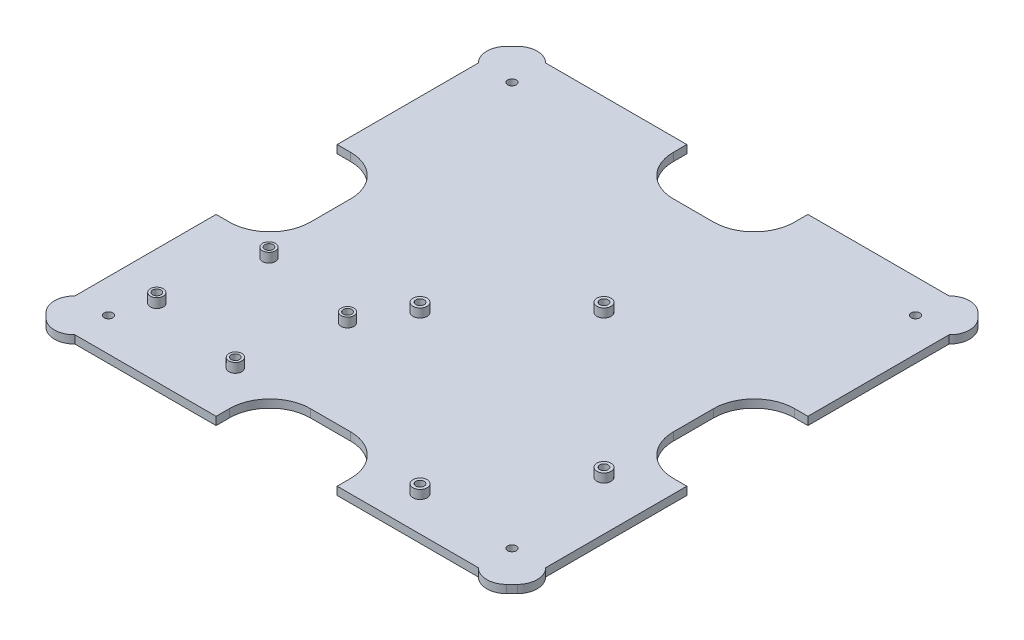
SolidWorks part; units mm, degrees
ref_plane "Front Plane" through (0, 0, 0) normal (0, 0, 1) x (1, 0, 0)
ref_plane "Top Plane" through (0, 0, 0) normal (0, 1, 0) x (1, 0, 0)
ref_plane "Right Plane" through (0, 0, 0) normal (1, 0, 0) x (0, 0, -1)
sketch "Sketch1" plane through (0, 0, 0) normal (0, 1, 0) x (1, 0, 0)
  line L0 (132.5, 75) -> (87.5, 75)
  line L5 (-75, 132.5) -> (75, 132.5)
  line L6 (-75, 132.5) -> (-75, 87.5)
  line L7 (-75, 87.5) -> (75, 87.5)
  line L8 (75, 132.5) -> (75, 87.5)
  line L9 (132.5, 75) -> (132.5, -75)
  line L10 (132.5, -75) -> (87.5, -75)
  line L11 (87.5, 75) -> (87.5, -75)
  line L12 (75, -132.5) -> (75, -87.5)
  line L13 (75, -132.5) -> (-75, -132.5)
  line L14 (-75, -132.5) -> (-75, -87.5)
  line L15 (75, -87.5) -> (-75, -87.5)
  line L16 (-132.5, -75) -> (-87.5, -75)
  line L17 (-132.5, -75) -> (-132.5, 75)
  line L18 (-132.5, 75) -> (-87.5, 75)
  line L19 (-87.5, -75) -> (-87.5, 75)
  line L20 (0, 122.5) -> (0, 87.5) construction
  line L21 (0, 132.5) -> (0, 122.5) construction
  circle A0 centre (0, 0) radius 122.5
  point P7 (0, 87.5)
  point P23 (0, 0)
  dimension "D1" = 245
  dimension "D4" = 35
  dimension "D2" = 150
  dimension "D5" = 10
  dimension "D3" = 4
extrude "shell-boss" add sketch "Sketch1" along normal blind 3 contours L12 A0 L10 L11 L0 L8 L7 L6 L18 L19 L16 L14 L15 region at (0, 0, 0)
fillet "shell-filet" radius 7.5 8 edges at (-96.8569, 1.5, 75) (-96.8569, 1.5, -75) (-75, 1.5, -96.8569) (75, 1.5, -96.8569) (96.8569, 1.5, -75) (96.8569, 1.5, 75) (75, 1.5, 96.8569) (-75, 1.5, 96.8569)
sketch "Sketch5" plane through (0, 3, 0) normal (0, 1, 0) x (1, 0, 0)
  line L2 (-87.5, 0) -> (87.5, 0) construction
  line L3 (-87.5, -75) -> (-87.5, 75) construction
  line L4 (87.5, 75) -> (87.5, -75) construction
  circle A0 centre (75, -75) radius 1.6
  circle A2 centre (-75, -75) radius 1.6
  arc A3 (85.6059, -87.6235) -> (87.6235, -85.6059) centre (0, 0) ccw construction
  circle A9 centre (75, 75) radius 1.6
  circle A10 centre (-75, 75) radius 1.6
  dimension "D1" = 150
  dimension "D2" = 3.2
  dimension "D4" = 106.066
  dimension "D3" = 150
extrude "shell-pillar-hole" cut sketch "Sketch5" against normal through all both and the other way through all
sketch "Sketch16" plane through (0, 3, 0) normal (0, 1, 0) x (1, 0, 0)
  line L0 (16.1138, 18.065) -> (-18.065, -16.1138) construction
  line L1 (16.1138, 18.065) -> (69.241, -35.0622) construction
  line L2 (69.241, -35.0622) -> (40.3605, -74.5394) construction
  line L3 (40.3605, -74.5394) -> (-18.065, -16.1138) construction
  line L4 (54.8008, -54.8008) -> (86.6206, -86.6206) construction
  line L5 (0, 0) -> (-86.6206, 86.6206) construction
  circle A4 centre (16.1138, 18.065) radius 2.625
  circle A5 centre (-18.065, -16.1138) radius 2.625
  circle A6 centre (69.241, -35.0622) radius 2.625
  circle A7 centre (40.3605, -74.5394) radius 2.625
  arc A8 (-85.6059, 87.6235) -> (-87.6235, 85.6059) centre (0, 0) ccw construction
  arc A9 (85.6059, -87.6235) -> (87.6235, -85.6059) centre (0, 0) ccw construction
  point P13 (-0.9756, 0.9756)
  dimension "D4" = 75.1332
  dimension "D2" = 48.3362
  dimension "D1" = 5.25
  dimension "D3" = 82.6262
  dimension "D5" = 45
extrude "arduino-mount-boss" add sketch "Sketch16" along normal blind 3.25
sketch "Sketch20" plane through (0, 3, 0) normal (0, 1, 0) x (1, 0, 0)
  line L0 (-37.2464, 19.4268) -> (-58.5183, -101.2121) construction
  line L1 (-63.6554, -26.6879) -> (-28.2023, -32.9392) construction
  line L2 (-28.2023, -32.9392) -> (-34.4536, -68.3923) construction
  line L3 (-34.4536, -68.3923) -> (-69.9067, -62.1409) construction
  line L4 (-69.9067, -62.1409) -> (-63.6554, -26.6879) construction
  line L9 (-52.1802, -65.2666) -> (-72.2702, -61.7242) construction
  line L11 (-52.1802, -65.2666) -> (-32.0901, -68.809) construction
  line L21 (-63.6554, -26.6879) -> (-63.2386, -24.3243) construction
  line L23 (-28.2023, -32.9392) -> (-27.7855, -30.5757) construction
  circle A16 centre (-63.6554, -26.6879) radius 2.4
  circle A17 centre (-28.2023, -32.9392) radius 2.4
  circle A18 centre (-34.4536, -68.3923) radius 2.4
  circle A19 centre (-69.9067, -62.1409) radius 2.4
  point P2 (-45.9288, -29.8135)
  dimension "D1" = 50
  dimension "D3" = 4.8
  dimension "D2" = 36
sketch "Sketch22" plane through (0, 6.25, 0) normal (0, 1, 0) x (1, 0, 0)
  circle A0 centre (16.1138, 18.065) radius 1.55
  circle A1 centre (-18.065, -16.1138) radius 1.55
  circle A2 centre (69.241, -35.0622) radius 1.55
  circle A3 centre (40.3605, -74.5394) radius 1.55
  dimension "D1" = 3.1
extrude "arduino-cut" cut sketch "Sketch22" against normal up to surface (6.25 mm away) up to face at (-75, 0, 76.6)
extrude "Boss-Extrude9" add sketch "Sketch20" along normal blind 3.5
sketch "Sketch37" plane through (0, 6.5, 0) normal (0, 1, 0) x (1, 0, 0)
  circle A0 centre (-63.6554, -26.6879) radius 1.55
  circle A1 centre (-28.2023, -32.9392) radius 1.55
  circle A2 centre (-69.9067, -62.1409) radius 1.55
  circle A3 centre (-34.4536, -68.3923) radius 1.55
  dimension "D1" = 3.1
extrude "Cut-Extrude4" cut sketch "Sketch37" against normal up to surface (6.5 mm away) up to face at (16.1138, 0, -16.515)
sketch "Sketch38" plane through (0, 0, 0) normal (0, -1, 0) x (1, 0, 0)
  line L0 (75, 87.5) -> (-75, 87.5) construction
  line L1 (22.5, 87.5) -> (-22.5, 87.5)
  line L2 (22.5, 87.5) -> (22.5, 67.5)
  line L3 (22.5, 67.5) -> (-22.5, 67.5)
  line L4 (-22.5, 87.5) -> (-22.5, 67.5)
  line L5 (87.5, -22.5) -> (67.5, -22.5)
  line L6 (87.5, -22.5) -> (87.5, 22.5)
  line L7 (87.5, 22.5) -> (67.5, 22.5)
  line L8 (67.5, -22.5) -> (67.5, 22.5)
  line L9 (-22.5, -87.5) -> (-22.5, -67.5)
  line L10 (-22.5, -87.5) -> (22.5, -87.5)
  line L11 (22.5, -87.5) -> (22.5, -67.5)
  line L12 (-22.5, -67.5) -> (22.5, -67.5)
  line L13 (-87.5, 22.5) -> (-67.5, 22.5)
  line L14 (-87.5, 22.5) -> (-87.5, -22.5)
  line L15 (-87.5, -22.5) -> (-67.5, -22.5)
  line L16 (-67.5, 22.5) -> (-67.5, -22.5)
  point P6 (0, 87.5)
  point P7 (0, 87.5)
  point P23 (0, 0)
  dimension "D1" = 45
  dimension "D2" = 20
  dimension "D3" = 4
extrude "Cut-Extrude5" cut sketch "Sketch38" against normal through all both and the other way through all
fillet "Fillet1" radius 15 8 edges at (-67.5, 1.5, -22.5) (-67.5, 1.5, 22.5) (22.5, 1.5, -67.5) (-22.5, 1.5, -67.5) (67.5, 1.5, -22.5) (67.5, 1.5, 22.5) (22.5, 1.5, 67.5) (-22.5, 1.5, 67.5)
